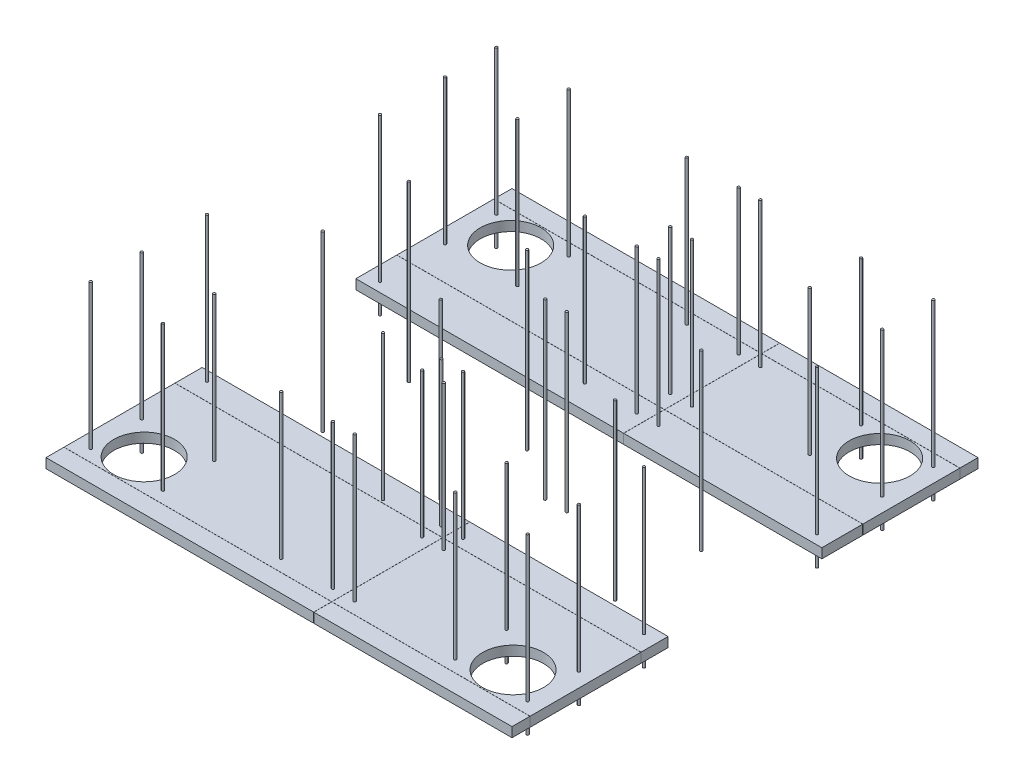
SolidWorks part; units mm, degrees
ref_plane "Front" through (0, 0, 0) normal (0, 0, 1) x (1, 0, 0)
ref_plane "Top" through (0, 0, 0) normal (0, 1, 0) x (1, 0, 0)
ref_plane "Right" through (0, 0, 0) normal (1, 0, 0) x (0, 0, -1)
sketch "Sketch1" plane through (0, 0, 0) normal (0, 1, 0) x (1, 0, 0)
  line L1 (-2454.275, 2454.275) -> (2454.275, 2454.275)
  line L2 (-2454.275, 2454.275) -> (-2454.275, -2454.275)
  line L3 (-2454.275, -2454.275) -> (2454.275, -2454.275)
  line L4 (2454.275, 2454.275) -> (2454.275, -2454.275)
  line L5 (-2454.275, 2454.275) -> (2454.275, -2454.275) construction
  line L6 (-2454.275, -2454.275) -> (2454.275, 2454.275) construction
  point P0 (0, 0)
  dimension "D1" = 4908.55
  dimension "D2" = 4908.55
extrude "Boss-Extrude1" add sketch "Sketch1" along normal blind 101.6
sketch "Sketch2" plane through (0, 101.6, 0) normal (0, 1, 0) x (1, 0, 0)
  line L0 (-2454.275, 2454.275) -> (-2454.275, -2454.275) construction
  line L1 (2454.275, -809.625) -> (-2454.275, -809.625)
  line L2 (2454.275, -809.625) -> (2454.275, 809.625)
  line L3 (2454.275, 809.625) -> (-2454.275, 809.625)
  line L4 (-2454.275, -809.625) -> (-2454.275, 809.625)
  line L5 (2454.275, -809.625) -> (-2454.275, 809.625) construction
  line L6 (2454.275, 809.625) -> (-2454.275, -809.625) construction
  point P0 (0, 0)
  dimension "D1" = 1619.25
extrude "Cut-Extrude1" cut sketch "Sketch2" against normal through all
sketch "Sketch4" plane through (0, 101.6, 0) normal (0, 1, 0) x (1, 0, 0)
  line L0 (-2454.275, -2263.775) -> (2454.275, -2263.775)
  line L3 (-2454.275, -2454.275) -> (2454.275, -2454.275) construction
  line L4 (-2454.275, -1095.375) -> (2454.275, -1095.375)
  line L5 (-2454.275, -809.625) -> (-2454.275, -2454.275) construction
  line L6 (-2454.275, -809.625) -> (2454.275, -809.625) construction
  line L7 (-2454.275, 2263.775) -> (2454.275, 2263.775)
  line L10 (-2454.275, 1241.425) -> (2454.275, 1241.425)
  line L11 (-2454.275, 2454.275) -> (-2454.275, 809.625) construction
  line L12 (2454.275, 809.625) -> (2454.275, 2454.275) construction
  line L13 (2454.275, 2454.275) -> (-2454.275, 2454.275) construction
  line L14 (2454.275, 809.625) -> (-2454.275, 809.625) construction
  line L15 (-2454.275, -1095.375) -> (-2454.275, -2263.775) construction
  line L16 (2454.275, -1095.375) -> (2454.275, -2263.775) construction
  line L17 (2454.275, 1241.425) -> (2454.275, 2263.775) construction
  line L18 (-2454.275, 1241.425) -> (-2454.275, 2263.775) construction
  line L19 (2454.275, -2454.275) -> (2454.275, -809.625) construction
  dimension "D1" = 190.5
  dimension "D2" = 1168.4
  dimension "D3" = 285.75
  dimension "D4" = 190.5
  dimension "D5" = 1022.35
  dimension "D6" = 431.8
extrude "Cut-Extrude-Thin1" cut sketch "Sketch4" against normal through all thin thin type one direction wall 1.27
sketch "Sketch5" plane through (0, 101.6, 0) normal (0, 1, 0) x (1, 0, 0)
  line L0 (365.125, -2454.275) -> (365.125, 2454.275)
  line L1 (-2454.275, -2454.275) -> (2454.275, -2454.275) construction
  line L2 (2454.275, 2454.275) -> (-2454.275, 2454.275) construction
  line L3 (2454.275, -2263.775) -> (2454.275, -1096.645) construction
  line L4 (-2454.275, -1096.645) -> (-2454.275, -2263.775) construction
  dimension "D1" = 2089.15
  dimension "D2" = 2819.4
extrude "Cut-Extrude-Thin2" cut sketch "Sketch5" against normal through all and the other way through all thin thin type one direction wall 1.27
sketch "Sketch8" plane through (0, 101.6, 0) normal (0, 1, 0) x (1, 0, 0)
  line L0 (-974.0807, 502.3386) -> (-974.0807, 1597.0052) construction
sketch "Sketch6" plane through (0, 101.6, 0) normal (0, 1, 0) x (1, 0, 0)
  line L0 (1943.1, 1929.13) -> (1943.1, 2262.505) construction
  line L1 (-1943.1, 1929.13) -> (1943.1, 1929.13) construction
  line L2 (-1943.1, 1929.13) -> (-1943.1, -1931.67) construction
  line L3 (-1943.1, -1931.67) -> (1943.1, -1931.67) construction
  line L4 (1943.1, 1929.13) -> (1943.1, -1931.67) construction
  line L5 (-1943.1, -1931.67) -> (-1943.1, -2265.045) construction
  line L6 (-2454.275, -2265.045) -> (365.125, -2265.045) construction
  line L7 (366.395, 2262.505) -> (2454.275, 2262.505) construction
  line L9 (2454.275, 1241.425) -> (2454.275, 2262.505) construction
  line L11 (-2454.275, -1096.645) -> (-2454.275, -2263.775) construction
  circle A0 centre (1943.1, 1929.13) radius 320.675
  circle A1 centre (-1943.1, 1929.13) radius 320.675
  circle A2 centre (-1943.1, -1931.67) radius 320.675
  circle A3 centre (1943.1, -1931.67) radius 320.675
  dimension "D1" = 641.35
  dimension "D3" = 190.5
  dimension "D4" = 190.5
  dimension "D2" = 12.7
extrude "DUCT HOLES" cut sketch "Sketch6" against normal through all
sketch "Sketch7" plane through (0, 101.6, 0) normal (0, 1, 0) x (1, 0, 0)
  line L0 (-1539.875, 2301.875) -> (-295.275, 2301.875) construction
  line L1 (-1539.875, 2301.875) -> (-2454.275, 2301.875) construction
  line L2 (-2454.275, 2454.275) -> (-2454.275, 2263.775) construction
  line L3 (365.125, 2454.275) -> (-2454.275, 2454.275) construction
  line L4 (-295.275, 2301.875) -> (365.125, 2301.875) construction
  line L5 (365.125, 2263.775) -> (365.125, 2454.275) construction
  line L6 (1539.875, 1597.025) -> (1539.875, 1063.625) construction
  line L7 (365.125, 2301.875) -> (974.725, 2301.875) construction
  line L8 (974.725, 2301.875) -> (1539.875, 2301.875) construction
  line L9 (1539.875, 2301.875) -> (2454.275, 2301.875) construction
  line L10 (2454.275, 2263.775) -> (2454.275, 2454.275) construction
  line L11 (366.395, 2263.775) -> (366.395, 2454.275) construction
  line L12 (2454.275, 1597.025) -> (-2454.275, 1597.025) construction
  line L13 (2454.275, 1241.425) -> (2454.275, 2262.505) construction
  line L14 (-2454.275, 2262.505) -> (-2454.275, 1241.425) construction
  line L15 (1539.875, 2301.875) -> (1539.875, 1597.025) construction
  line L16 (-2454.275, 1241.425) -> (365.125, 1241.425) construction
  line L17 (-295.275, 2301.875) -> (-295.275, 1597.025) construction
  line L18 (974.725, 2301.875) -> (974.725, 1597.025) construction
  line L19 (-2454.275, 2136.775) -> (2454.275, 2136.775) construction
  line L20 (-2454.275, 2263.775) -> (365.125, 2263.775) construction
  line L21 (-1539.875, 2301.875) -> (-1539.875, 2136.775) construction
  line L22 (-2454.275, 1063.625) -> (2454.275, 1063.625) construction
  line L23 (-2454.275, 1240.155) -> (-2454.275, 809.625) construction
  line L24 (2454.275, 809.625) -> (2454.275, 1240.155) construction
  line L25 (365.125, 809.625) -> (-2454.275, 809.625) construction
  line L26 (-1539.875, 1063.625) -> (-1539.875, 1597.025) construction
  line L27 (-295.275, 1597.025) -> (-295.275, 1063.625) construction
  line L28 (-2107.4102, -2022.1425) -> (-2107.4102, -819.4758) construction
  line L29 (-1539.875, 1285.875) -> (1539.875, 1285.875) construction
  line L30 (-2301.875, 1597.025) -> (-2301.875, 1063.625) construction
  line L31 (2301.875, 1597.025) -> (2301.875, 1063.625) construction
  line L32 (-2454.275, 1240.155) -> (365.125, 1240.155) construction
  line L33 (479.425, 1063.625) -> (250.825, 1063.625) construction
  line L34 (479.425, 1063.625) -> (479.425, 1416.685) construction
  line L35 (479.425, 1416.685) -> (250.825, 1416.685) construction
  line L36 (250.825, 1063.625) -> (250.825, 1416.685) construction
  line L37 (-2454.275, 1240.155) -> (365.125, 1240.155) construction
  line L38 (365.125, 809.625) -> (365.125, 1240.155) construction
  line L39 (365.125, 809.625) -> (365.125, 1240.155) construction
  line L40 (440.6472, 1241.425) -> (440.6472, 1063.625) construction
  line L41 (250.825, -1198.245) -> (479.425, -1198.245) construction
  line L42 (250.825, -1198.245) -> (250.825, -995.045) construction
  line L43 (250.825, -995.045) -> (479.425, -995.045) construction
  line L44 (479.425, -1198.245) -> (479.425, -995.045) construction
  line L45 (366.395, 1241.425) -> (2454.275, 1241.425) construction
  line L46 (1539.875, 1063.625) -> (1539.875, -2454.275) construction
  line L47 (366.395, -2454.275) -> (2454.275, -2454.275) construction
  line L48 (-2454.275, -1096.645) -> (365.125, -1096.645) construction
  line L49 (-2454.275, -1096.645) -> (365.125, -1096.645) construction
  line L50 (-2301.875, 1063.625) -> (-2301.875, 911.225) construction
  line L51 (-2301.875, 911.225) -> (2301.875, 911.225) construction
  line L52 (2301.875, 911.225) -> (2301.875, 1063.625) construction
  line L53 (-1539.875, 1063.625) -> (-1539.875, -2454.275) construction
  line L54 (-2454.275, -2454.275) -> (365.125, -2454.275) construction
  line L55 (1539.875, 454.025) -> (-1539.875, 454.025) construction
  line L56 (250.825, 1063.625) -> (250.825, -2454.275) construction
  line L57 (479.425, 1063.625) -> (479.425, -2454.275) construction
  line L58 (-295.275, 1063.625) -> (-295.275, -2454.275) construction
  line L59 (479.425, 98.425) -> (250.825, 98.425) construction
  line L60 (479.425, 1063.625) -> (479.425, 2301.875) construction
  line L61 (250.825, 1063.625) -> (250.825, 2301.875) construction
  circle A0 centre (-1539.875, 2301.875) radius 12.7 construction
  circle A4 centre (1539.875, 1597.025) radius 12.7
  circle A5 centre (-1539.875, 1597.025) radius 12.7
  circle A6 centre (479.425, 1063.625) radius 12.7
  circle A7 centre (-295.275, 1597.025) radius 12.7 construction
  circle A8 centre (974.725, 1597.025) radius 12.7 construction
  circle A9 centre (-295.275, 2136.775) radius 12.7
  circle A10 centre (-1539.875, 2136.775) radius 12.7
  circle A11 centre (974.725, 2136.775) radius 12.7 construction
  circle A12 centre (1539.875, 2136.775) radius 12.7
  circle A13 centre (-295.275, 1063.625) radius 12.7
  circle A14 centre (-1539.875, 1063.625) radius 12.7 construction
  circle A15 centre (1539.875, 1063.625) radius 12.7 construction
  circle A16 centre (-2301.875, 1597.025) radius 12.7
  circle A17 centre (2301.875, 1597.025) radius 12.7
  circle A18 centre (-2301.875, 2136.775) radius 12.7
  circle A19 centre (2301.875, 2136.775) radius 12.7
  circle A20 centre (219.075, 2301.875) radius 12.7 construction
  circle A21 centre (658.495, 2301.875) radius 12.7 construction
  circle A22 centre (1539.875, 2301.875) radius 12.7 construction
  circle A23 centre (-650.875, 2301.875) radius 12.7 construction
  circle A24 centre (-1539.875, 1285.875) radius 12.7 construction
  circle A25 centre (1539.875, 1285.875) radius 12.7 construction
  circle A26 centre (-2301.875, 1063.625) radius 12.7 construction
  circle A27 centre (2301.875, 1063.625) radius 12.7 construction
  circle A28 centre (250.825, 1416.685) radius 12.7
  circle A29 centre (479.425, 1416.685) radius 12.7
  circle A30 centre (250.825, 1063.625) radius 12.7
  circle A31 centre (479.425, -995.045) radius 12.7
  circle A32 centre (250.825, -995.045) radius 12.7
  circle A33 centre (250.825, -1198.245) radius 12.7
  circle A34 centre (479.425, -1198.245) radius 12.7
  circle A35 centre (-2301.875, 911.225) radius 12.7
  circle A36 centre (2301.875, 911.225) radius 12.7
  circle A37 centre (1539.875, 454.025) radius 12.7
  circle A38 centre (-1539.875, 454.025) radius 12.7
  circle A41 centre (-295.275, 454.025) radius 12.7
  circle A43 centre (479.425, 98.425) radius 12.7
  circle A44 centre (250.825, 98.425) radius 12.7
  circle A45 centre (250.825, 2136.775) radius 12.7
  circle A47 centre (479.425, 2136.775) radius 12.7
  point P107 (250.825, -1096.645)
  dimension "D1" = 25.4
  dimension "D5" = 609.6
  dimension "D7" = 355.6
  dimension "D11" = 152.4
  dimension "D14" = 152.4
  dimension "D19" = 889
  dimension "D20" = 914.4
  dimension "D21" = 1168.4
  dimension "D25" = 457.2
  dimension "D26" = 355.6
  dimension "D2" = 152.4
  dimension "D3" = 914.4
  dimension "D4" = 660.4
  dimension "D6" = 914.4
  dimension "D8" = 914.4
  dimension "D9" = 127
  dimension "D10" = 152.4
  dimension "D12" = 254
  dimension "D13" = 228.6
  dimension "D15" = 152.4
  dimension "D16" = 146.05
  dimension "D17" = 292.1
  dimension "D18" = 914.4
  dimension "D22" = 3079.75
  dimension "D23" = 203.2
  dimension "D24" = 152.4
extrude "UNISTRUT STUD LAYOUT" add sketch "Sketch7" along normal blind 1524 and the other way blind 304.8 separate body
mirror "Mirror3" about plane through (0, 0, 0) normal (0, 0, 1) of bodies 251 238 222 252 271 272 286 302 301 306 309 305 316 315 317 320 321 240 223 227 214 225 241 215 226 224 228 217 244 229 216 275 276 277 281 283 287 288 293 291
